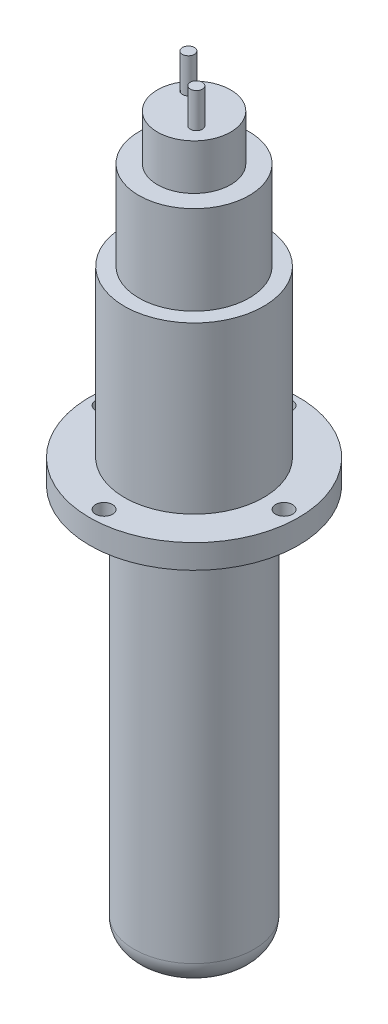
SolidWorks part; units mm, degrees
material "6061 Alloy"
ref_plane "Front" through (0, 0, 0) normal (0, 0, 1) x (1, 0, 0)
ref_plane "Top" through (0, 0, 0) normal (0, 1, 0) x (1, 0, 0)
ref_plane "Right" through (0, 0, 0) normal (1, 0, 0) x (0, 0, -1)
sketch "Sketch1" plane through (0, 0, 0) normal (0, 1, 0) x (1, 0, 0)
  circle A0 centre (0, 0) radius 22.098
  dimension "D1" = 44.196
extrude "Boss-Extrude1" add sketch "Sketch1" along normal blind 5.08
sketch "Sketch2" plane through (0, 5.08, 0) normal (0, 1, 0) x (1, 0, 0)
  circle A0 centre (0, 0) radius 14.732
  dimension "D1" = 29.464
extrude "Boss-Extrude2" add sketch "Sketch2" along normal blind 35.052
sketch "Sketch3" plane through (0, 40.132, 0) normal (0, 1, 0) x (1, 0, 0)
  circle A0 centre (0, 0) radius 11.684
  dimension "D1" = 23.368
extrude "Boss-Extrude3" add sketch "Sketch3" along normal blind 18.796
sketch "Sketch4" plane through (0, 58.928, 0) normal (0, 1, 0) x (1, 0, 0)
  circle A0 centre (0, 0) radius 7.747
  dimension "D1" = 15.494
extrude "Boss-Extrude4" add sketch "Sketch4" along normal blind 9.652
sketch "Sketch5" plane through (0, 68.58, 0) normal (0, 1, 0) x (1, 0, 0)
  circle A0 centre (-4.2434, 3.0444) radius 1.27
  circle A1 centre (2.97, -2.4818) radius 1.27
  dimension "D1" = 2.54
  dimension "D2" = 2.54
extrude "Boss-Extrude5" add sketch "Sketch5" along normal blind 7.366
sketch "Sketch6" plane through (0, 5.08, 0) normal (0, 1, 0) x (1, 0, 0)
  circle A0 centre (0, 19.05) radius 1.7907
  point P2 (0, 19.05)
  point P3 (0, 0)
  point P5 (0, 0)
  dimension "D1" = 3.5814
  dimension "D2" = 19.05
extrude "Cut-Extrude1" cut sketch "Sketch6" against normal blind 7.366
pattern_circular "CirPattern1" count 4 over 360 about axis through (0, 5.08, 0) along (0, 1, 0) of "Cut-Extrude1"
sketch "Sketch7" plane through (0, 0, 0) normal (0, -1, 0) x (-1, 0, 0)
  circle A0 centre (0, 0) radius 12.7
  dimension "D1" = 25.4
extrude "Boss-Extrude6" add sketch "Sketch7" along normal blind 83.82
fillet "Fillet1" radius 5.08 1 edges at (0, -83.82, -12.7)
